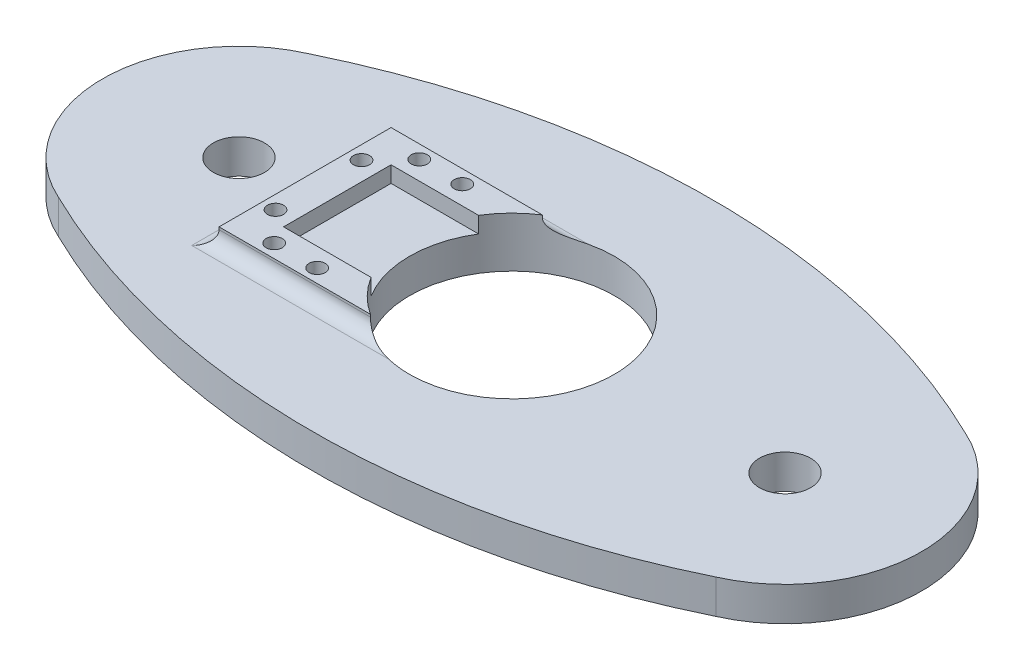
SolidWorks part; units mm, degrees
ref_plane "Front Plane" through (0, 0, 0) normal (0, 0, 1) x (1, 0, 0)
ref_plane "Top Plane" through (0, 0, 0) normal (0, 1, 0) x (1, 0, 0)
ref_plane "Right Plane" through (0, 0, 0) normal (1, 0, 0) x (0, 0, -1)
sketch "Sketch1" plane through (0, 0, 0) normal (0, 1, 0) x (1, 0, 0)
  circle A0 centre (0, 0) radius 76.2
  dimension "D1" = 152.4
extrude "Boss-Extrude1" add sketch "Sketch1" along normal blind 6.35
sketch "Sketch2" plane through (0, 6.35, 0) normal (0, 1, 0) x (1, 0, 0)
  line L0 (0, -3.4925) -> (0, 3.4925) construction
  line L1 (-50.8, -25.4) -> (50.8, -25.4)
  line L3 (-50.8, 25.4) -> (50.8, 25.4)
  line L4 (71.842, -14.2265) -> (71.842, 14.2265)
  line L5 (-63.0049, -22.2756) -> (63.0049, 22.2756) construction
  line L6 (-63.0049, 22.2756) -> (63.0049, -22.2756) construction
  circle A0 centre (0, 0) radius 76.2 construction
  circle A1 centre (-50.8, 0) radius 4.7625
  circle A2 centre (50.8, 0) radius 4.7625
  circle A3 centre (-50.8, 0) radius 25.4
  circle A4 centre (50.8, 0) radius 25.4
  circle A5 centre (0, 0) radius 19.05
  arc A6 (-63.0049, 22.2756) -> (63.0049, 22.2756) centre (0, -102.4099) cw
  arc A7 (-63.0049, -22.2756) -> (63.0049, -22.2756) centre (0, 102.4099) ccw
  point P0 (0, 0)
  circle M2 centre (0, 0) radius 76.2
  dimension "D2" = 9.525
  dimension "D3" = 50.8
extrude "Cut-Extrude2" cut sketch "Sketch2" against normal blind 6.35 contours A4 A3 L3 M2 | A4 L1 A3 M2 | A1 | A2 | A5 region at (0, 6.35, 48.4705) region at (0, 6.35, -48.4705) region at (-50.8, 6.35, 0) region at (50.8, 6.35, 0) region at (0, 6.35, 0)
sketch "Sketch3" plane through (0, 6.35, 0) normal (0, 1, 0) x (1, 0, 0)
  line L0 (-38.5, -4.75) -> (-38.5, -11.25) construction
  line L1 (-18, -16) -> (-11.5, -16) construction
  line L2 (-38.5, 11.25) -> (-38.5, 4.75) construction
  line L3 (-11.5, 16) -> (-18, 16) construction
  line L4 (-38.5, -4.75) -> (-38.5, -11.25)
  line L5 (-18, -16) -> (-11.5, -16)
  line L6 (-38.5, 11.25) -> (-38.5, 4.75)
  line L7 (-11.5, 16) -> (-18, 16)
  line L8 (-18, 16) -> (-38.5, 16)
  line L9 (-38.5, 16) -> (-38.5, -16)
  line L10 (-38.5, -16) -> (-11.5, -16)
  line L11 (-11.5, 16) -> (-10.3394, 16)
  line L12 (-11.5, -16) -> (-10.3394, -16)
  line L13 (-31.0963, -10) -> (-8.95, -10) construction
  line L14 (-8.95, 10) -> (-31.0279, 10) construction
  line L15 (-32.5, 8.4256) -> (-32.5, -8.5229) construction
  line L16 (-31.0963, -10) -> (-8.95, -10)
  line L17 (-8.95, 10) -> (-31.0279, 10)
  line L18 (-32.5, 8.4256) -> (-32.5, -8.5229)
  line L19 (-31.0963, -10) -> (-32.5, -10)
  line L20 (-32.5, -10) -> (-32.5, -8.5229)
  line L21 (-31.0279, 10) -> (-32.5, 10)
  line L22 (-32.5, 10) -> (-32.5, 8.4256)
  circle A0 centre (0, 0) radius 19.05 construction
  circle M1 centre (0, 0) radius 19.05
extrude "Boss-Extrude2" add sketch "Sketch3" along normal up to surface (3 mm away) contours L22 L21 L17 L11 L7 L8 L9 L6 L4 L10 L5 L12 L16 L19 L20 L18 M1 region at (-38.0737, 6.35, 0)
sketch "Sketch4" plane through (0, 9.35, 0) normal (0, 1, 0) x (1, 0, 0)
  circle A0 centre (-22.75, -13.5) radius 1.25 construction
  circle A1 centre (-30.75, -13.5) radius 1.25 construction
  circle A2 centre (-36, -8) radius 1.25 construction
  circle A3 centre (-36, 8) radius 1.25 construction
  circle A4 centre (-30.75, 13.5) radius 1.25 construction
  circle A5 centre (-22.75, 13.5) radius 1.25 construction
  circle A6 centre (-22.75, -13.5) radius 1.25
  circle A7 centre (-30.75, -13.5) radius 1.25
  circle A8 centre (-36, -8) radius 1.25
  circle A9 centre (-36, 8) radius 1.25
  circle A10 centre (-30.75, 13.5) radius 1.25
  circle A11 centre (-22.75, 13.5) radius 1.25
  circle A12 centre (-30.75, 13.5) radius 1.5
  circle A13 centre (-22.75, 13.5) radius 1.5
  circle A14 centre (-36, 8) radius 1.5
  circle A15 centre (-36, -8) radius 1.5
  circle A16 centre (-30.75, -13.5) radius 1.5
  circle A17 centre (-22.75, -13.5) radius 1.5
extrude "Cut-Extrude3" cut sketch "Sketch4" against normal through all contours A6 | A7 | A8 | A9 | A11 | A10 | A16 A7 | A17 A6 | A15 A8 | A14 A9 | A12 A10 | A13 A11 region at (-22.75, 9.35, 13.5) region at (-30.75, 9.35, 13.5) region at (-36, 9.35, 8) region at (-36, 9.35, -8) region at (-30.75, 9.35, -13.5) region at (-22.75, 9.35, -13.5) region at (-32.2076, 9.35, -13.5) region at (-24.2076, 9.35, -13.5) region at (-37.4576, 9.35, -8) region at (-37.4576, 9.35, 8) region at (-32.2076, 9.35, 13.5) region at (-24.2076, 9.35, 13.5)
fillet "Fillet1" radius 2.54 3 edges at (-24.4197, 6.35, -16) (-38.5, 6.35, 0) (-24.4197, 6.35, 16)
sketch "Sketch5" plane through (0, 0, 0) normal (0, -1, 0) x (1, 0, 0)
  circle A0 centre (-22.75, 13.5) radius 2.5
  circle A1 centre (-30.75, 13.5) radius 2.5
  circle A2 centre (-36, 8) radius 2.5
  circle A3 centre (-36, -8) radius 2.5
  circle A4 centre (-30.75, -13.5) radius 2.5
  circle A5 centre (-22.75, -13.5) radius 2.5
extrude "Cut-Extrude4" cut sketch "Sketch5" against normal blind 2.85
